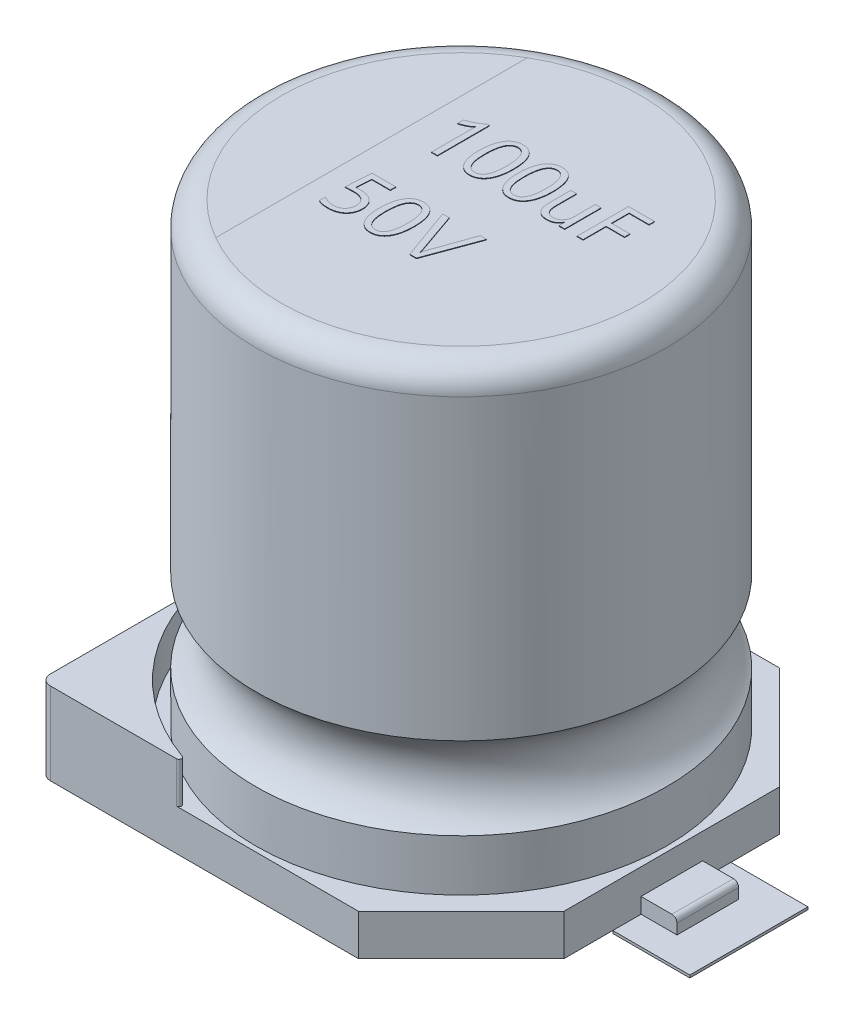
SolidWorks part; units mm, degrees
ref_plane "Front Plane" through (0, 0, 0) normal (0, 0, 1) x (1, 0, 0)
ref_plane "Top Plane" through (0, 0, 0) normal (0, 1, 0) x (1, 0, 0)
ref_plane "Right Plane" through (0, 0, 0) normal (1, 0, 0) x (0, 0, -1)
sketch "Sketch1" plane through (0, 0, 0) normal (0, 1, 0) x (1, 0, 0)
  circle A0 centre (0, 0) radius 4
  dimension "D1" = 8
extrude "Boss-Extrude1" add sketch "Sketch1" along normal blind 8.9
sketch "Sketch2" plane through (0, 0, 0) normal (0, 0, 1) x (1, 0, 0)
  line L0 (-4, 8.9) -> (-4, 0) construction
  line L1 (-4, 2.6) -> (-4, 1)
  line L2 (0, 0) -> (0, 2.8507) construction
  arc A0 (-4, 2.6) -> (-4, 1) centre (-4.6, 1.8) cw
  dimension "D1" = 1
  dimension "D2" = 1
  dimension "D3" = 0.6
revolve "Cut-Revolve1" cut sketch "Sketch2" angle 360 about L2
fillet "Fillet1" radius 0.5 1 edges at (0, 8.9, 4)
sketch "Sketch3" plane through (0, 0, 0) normal (0, -1, 0) x (1, 0, 0)
  line L1 (4.1, -4.1) -> (-4.1, -4.1)
  line L2 (4.1, -4.1) -> (4.1, 4.1)
  line L3 (4.1, 4.1) -> (-4.1, 4.1)
  line L4 (-4.1, -4.1) -> (-4.1, 4.1)
  line L5 (4.1, -4.1) -> (-4.1, 4.1) construction
  line L6 (4.1, 4.1) -> (-4.1, -4.1) construction
  circle A0 centre (0, 0) radius 4 construction
  point P0 (0, 0)
  dimension "D1" = 4.1
  dimension "D2" = 4.1
extrude "Boss-Extrude2" add sketch "Sketch3" along normal blind 0.8 separate body
chamfer "Chamfer1" distance 2 angle 45 2 edges at (4.1, -0.4, -4.1) (4.1, -0.4, 4.1)
sketch "Sketch4" plane through (0, 0, 0) normal (0, 1, 0) x (1, 0, 0)
  line L0 (2.1, -4.1) -> (-4.1, -4.1) construction
  line L1 (-4.1, -4.1) -> (-4.1, 4.1) construction
  line L2 (-4.1, 4.1) -> (2.1, 4.1) construction
  line L3 (-1.1192, -4.1) -> (-4.1, -4.1)
  line L4 (-4.1, -4.1) -> (-4.1, -1.1192)
  line L5 (-4.1, 4.1) -> (-1.1192, 4.1)
  line L6 (-4.1, 1.1192) -> (-4.1, 4.1)
  arc A0 (-4.1, -1.1192) -> (-1.1192, -4.1) centre (0, 0) ccw
  arc A1 (-1.1192, 4.1) -> (-4.1, 1.1192) centre (0, 0) ccw
  dimension "D1" = 8.5
extrude "Boss-Extrude3" add sketch "Sketch4" along normal blind 0.8
fillet "Fillet2" radius 0.05 4 edges at (-1.1192, 0.4, -4.1) (-4.1, 0.4, -1.1192) (-4.1, 0.4, 1.1192) (-1.1192, 0.4, 4.1)
sketch "Sketch5" plane through (-4.1, 0, 0) normal (-1, 0, 0) x (0, 0, 1)
  line L0 (4.1, -0.8) -> (-4.1, -0.8) construction
  line L1 (-0.6, -0.8) -> (0.6, -0.8)
  line L2 (-0.6, -0.8) -> (-0.6, -0.5)
  line L3 (-0.6, -0.5) -> (0.6, -0.5)
  line L4 (0.6, -0.8) -> (0.6, -0.5)
  point P6 (0, -0.5)
  dimension "D1" = 1.2
  dimension "D2" = 0.3
extrude "Boss-Extrude4" add sketch "Sketch5" along normal blind 0.7 separate body
fillet "Fillet3" radius 0.1 1 edges at (-4.8, -0.5, 0)
mirror "Mirror3" about plane through (0, 0, 0) normal (1, 0, 0) of bodies 106
fillet "Fillet4" radius 0.2 2 edges at (-4.1, 0, -4.1) (-4.1, 0, 4.1)
sketch "Sketch6" plane through (0, 8.9, 0) normal (0, 1, 0) x (1, 0, 0)
  line L0 (-1.7448, 3.0341) -> (-1.7448, -3.0341)
  circle A0 centre (0, 0) radius 3.5 construction
split line "Split Line1"
sketch "Sketch7" plane through (0, 8.9, 0) normal (0, 1, 0) x (1, 0, 0)
  text T0 "100uF" font "Yu Gothic UI" height 1
  text T1 "50V" font "Yu Gothic UI" height 1
extrude "Boss-Extrude5" add sketch "Sketch7" along normal blind 0.01
sketch "Sketch8" plane through (0, -0.8, 0) normal (0, -1, 0) x (1, 0, 0)
  line L0 (-4.1, 3.9) -> (-4.1, -3.9) construction
  line L1 (-4.1, 1.15) -> (-5.6, 1.15)
  line L2 (-4.1, 1.15) -> (-4.1, -1.15)
  line L3 (-4.1, -1.15) -> (-5.6, -1.15)
  line L4 (-5.6, 1.15) -> (-5.6, -1.15)
  line L5 (0, 0) -> (0, 1.5788) construction
  line L6 (5.6, 1.15) -> (5.6, -1.15)
  line L7 (4.1, -1.15) -> (5.6, -1.15)
  line L8 (4.1, 1.15) -> (4.1, -1.15)
  line L9 (4.1, 1.15) -> (5.6, 1.15)
  point P6 (-5.6, 0)
  dimension "D1" = 2.3
  dimension "D2" = 1.5
extrude "Boss-Extrude6" add sketch "Sketch8" along normal blind 0.05 separate body
